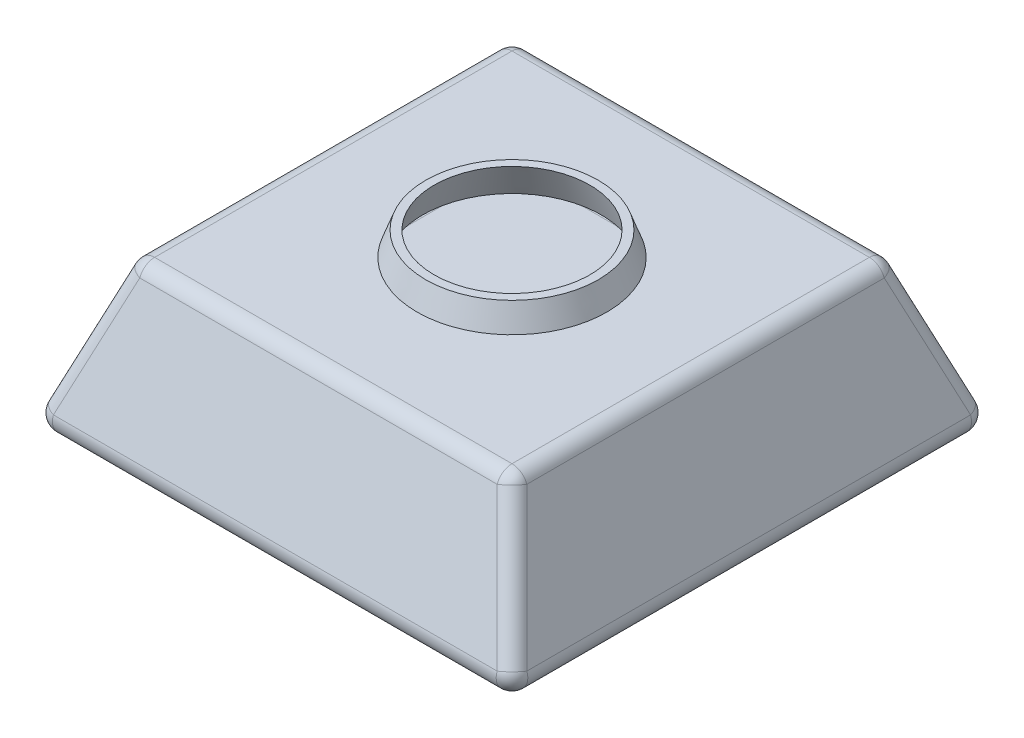
SolidWorks part; units mm, degrees
ref_plane "Front Plane" through (0, 0, 0) normal (0, 0, 1) x (1, 0, 0)
ref_plane "Top Plane" through (0, 0, 0) normal (0, 1, 0) x (1, 0, 0)
ref_plane "Right Plane" through (0, 0, 0) normal (1, 0, 0) x (0, 0, -1)
sketch "Sketch1" plane through (0, 0, 0) normal (0, 1, 0) x (1, 0, 0)
  line L1 (0, 0) -> (480, 0)
  line L2 (0, 0) -> (0, -480)
  line L3 (0, -480) -> (480, -480)
  line L4 (480, 0) -> (480, -480)
  dimension "D1" = 480
  dimension "D2" = 480
extrude "Boss-Extrude1" add sketch "Sketch1" against normal blind 190 draft 20 contours L1 L4 L3 L2 draft outward yes
fillet "Fillet1" radius 20 12 edges at (-34.5772, -95, -34.5772) (514.5772, -95, -34.5772) (549.1543, -190, 240) (240, -190, -69.1543) (-69.1543, -190, 240) (514.5772, -95, 514.5772) (240, -190, 549.1543) (-34.5772, -95, 514.5772) (240, 0, 0) (480, 0, 240) (240, 0, 480) (0, 0, 240)
sketch "Sketch2" plane through (0, 0, 0) normal (0, 1, 0) x (1, 0, 0)
  line L0 (14.0042, -14.0042) -> (465.9958, -465.9958) construction
  circle A0 centre (240, -240) radius 120
  dimension "D1" = 240
extrude "Boss-Extrude2" add sketch "Sketch2" along normal blind 30 draft 20
shell "Shell1" thickness 10 removed face at (240, 30, 349.0809)
